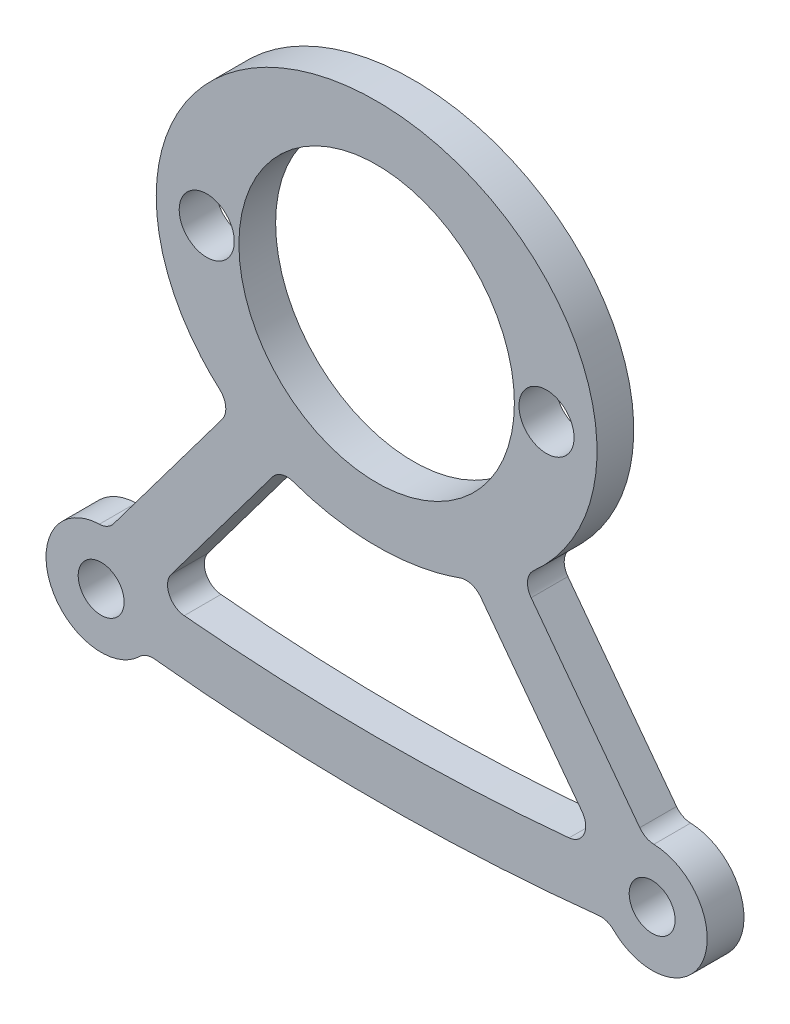
SolidWorks part; units mm, degrees
material "A2017"
ref_plane "正面" through (0, 0, 0) normal (0, 0, 1) x (1, 0, 0)
ref_plane "平面" through (0, 0, 0) normal (0, 1, 0) x (1, 0, 0)
ref_plane "右側面" through (0, 0, 0) normal (1, 0, 0) x (0, 0, -1)
sketch "ｽｹｯﾁ1" plane through (0, 0, 0) normal (0, 0, 1) x (1, 0, 0)
  line L0 (-15, -20) -> (0, -20) construction
  line L1 (0, -20) -> (0, 0) construction
  line L2 (0, 0) -> (9.25, 0) construction
  line L3 (6.5, 0) -> (7.5, 0) construction
  circle A0 centre (0, 0) radius 7.5
  circle A1 centre (-15, -20) radius 3
  circle A2 centre (-15, -20) radius 1
  circle A3 centre (15, -20) radius 1
  circle A4 centre (15, -20) radius 3
  circle A5 centre (0, 0) radius 10.5 construction
  circle A6 centre (9.25, 0) radius 2.75 construction
  circle A7 centre (9.25, 0) radius 1.5
  circle A8 centre (9.25, 0) radius 2.75 construction
  circle A9 centre (-9.25, 0) radius 1.5
  ellipse E0 centre (0, 0) end of major axis (12, 0) minor radius 10.5
  dimension "D1" = 15
  dimension "D2" = 20
  dimension "D3" = 15
  dimension "D4" = 6
  dimension "D5" = 2
  dimension "D7" = 5.5
  dimension "D9" = 3
  dimension "D10" = 5.5
  dimension "D6" = 3
  dimension "D8" = 1
extrude "ﾎﾞｽ - 押し出し1" add sketch "ｽｹｯﾁ1" along normal blind 2
sketch "ｽｹｯﾁ7" plane through (0, 0, 2) normal (0, 0, 1) x (1, 0, 0)
  line L0 (-15, -21) -> (15, -21) construction
  line L1 (0, 0) -> (-15, -20) construction
  line L2 (-7.838, -7.9507) -> (-14.6412, -17.0215)
  line L3 (-5.2169, -9.4558) -> (-12.2412, -18.8215)
  line L4 (0, 0) -> (0, -21) construction
  line L5 (-1.2, 0.9) -> (-16.2, -19.1) construction
  line L6 (1.2, -0.9) -> (-13.8, -20.9) construction
  line L7 (0, 0) -> (15, -20) construction
  line L8 (5.2169, -9.4558) -> (12.2412, -18.8215)
  line L9 (7.838, -7.9507) -> (14.6412, -17.0215)
  arc A0 (-15, -20) -> (15, -20) centre (0, 92) ccw construction
  circle A1 centre (-15, -20) radius 1 construction
  circle A2 centre (15, -20) radius 1 construction
  arc A3 (-12.6032, -21.8043) -> (12.6032, -21.8043) centre (0, 92) ccw
  arc A4 (-12.2392, -18.8262) -> (12.2392, -18.8262) centre (0, 92) ccw
  circle A5 centre (-15, -20) radius 3 construction
  circle A6 centre (15, -20) radius 3 construction
  arc A7 (-12.6032, -21.8043) -> (-12.2392, -18.8262) centre (-15, -20) ccw
  arc A8 (12.2392, -18.8262) -> (12.6032, -21.8043) centre (15, -20) ccw
  arc A9 (-14.6412, -17.0215) -> (-12.2412, -18.8215) centre (-15, -20) cw
  arc A10 (-14.8009, -18.5133) -> (14.8009, -18.5133) centre (0, 92) ccw construction
  arc A11 (14.6412, -17.0215) -> (12.2412, -18.8215) centre (15, -20) ccw
  arc A12 (-15.1991, -21.4867) -> (15.1991, -21.4867) centre (0, 92) ccw construction
  ellipse E0 centre (0, 0) end of major axis (12, 0) minor radius 10.5 construction
  ellipse E1 centre (0, 0) end of major axis (12, 0) minor radius 10.5 (-7.838, -7.9507) -> (-5.2169, -9.4558) ccw
  ellipse E2 centre (0, 0) end of major axis (-12, 0) minor radius 10.5 (7.838, -7.9507) -> (5.2169, -9.4558) cw
  dimension "D1" = 1.5
  dimension "D3" = 1.5
  dimension "D2" = 1.5
  dimension "D4" = 1.5
extrude "ﾎﾞｽ - 押し出し3" add sketch "ｽｹｯﾁ7" against normal up to surface (2 mm away) up to face at (12, 0, 0)
fillet "ﾌｨﾚｯﾄ3" radius 1 8 edges at (7.838, -7.9507, 1) (-14.6412, -17.0215, 1) (14.6412, -17.0215, 1) (12.6032, -21.8043, 1) (-12.6032, -21.8043, 1) (5.2169, -9.4558, 1)
sketch "ｽｹｯﾁ8" plane through (0, 0, 2) normal (0, 0, 1) x (1, 0, 0)
  line L0 (-12.2412, -18.8215) -> (-5.6721, -10.0628) construction
  line L1 (-12.2412, -18.8215) -> (-11.1833, -17.4111)
  line L2 (0, 0) -> (0, -19.5) construction
  line L3 (12.2412, -18.8215) -> (11.1833, -17.4111)
  arc A0 (-11.1833, -17.4111) -> (-10.4773, -19.0067) centre (-10.3833, -18.0111) ccw
  arc A1 (-12.2392, -18.8262) -> (12.2392, -18.8262) centre (0, 92) ccw construction
  arc A2 (-12.2392, -18.8262) -> (-12.2412, -18.8215) centre (-15, -20) ccw construction
  arc A3 (-12.2392, -18.8262) -> (-12.2412, -18.8215) centre (-15, -20) ccw
  arc A4 (-12.2392, -18.8262) -> (-10.4773, -19.0067) centre (0, 92) ccw
  arc A5 (12.2392, -18.8262) -> (10.4773, -19.0067) centre (0, 92) cw
  arc A6 (12.2392, -18.8262) -> (12.2412, -18.8215) centre (15, -20) cw
  arc A7 (11.1833, -17.4111) -> (10.4773, -19.0067) centre (10.3833, -18.0111) cw
  dimension "D1" = 2
extrude "ﾎﾞｽ - 押し出し4" add sketch "ｽｹｯﾁ8" against normal up to surface (2 mm away) up to face at (0.466, -16.2599, 0)
hole_wizard "M3 ねじ穴1" positions "ｽｹｯﾁ9" profile "ｽｹｯﾁ10" tap size "M3" standard "JIS" end condition through all
sketch "ｽｹｯﾁ9" plane through (0, 0, 0) normal (0, 0, -1) x (-1, 0, 0)
  point P0 (-15, -20)
  point P3 (15, -20)
sketch "ｽｹｯﾁ10" plane through (15, -20, 0) normal (1, 0, 0) x (0, 1, 0)
  line L0 (0, 0) -> (0, 2)
  line L1 (0, 2) -> (1.25, 2)
  line L2 (1.25, 2) -> (1.25, 0)
  line L5 (1.25, 0) -> (0, 0)
  line L11 (0, -6.35) -> (0, 107.95) construction
  dimension "次ｻｰﾌｪｽまでのねじ下穴ﾄﾞﾘﾙ直径" = 2.5
  dimension "次ｻｰﾌｪｽまでのねじ下穴ﾄﾞﾘﾙの深さ" = 2
cosmetic thread "穴のねじ山1" parameters "D2"=3
cosmetic thread "穴のねじ山2" parameters "D2"=3
